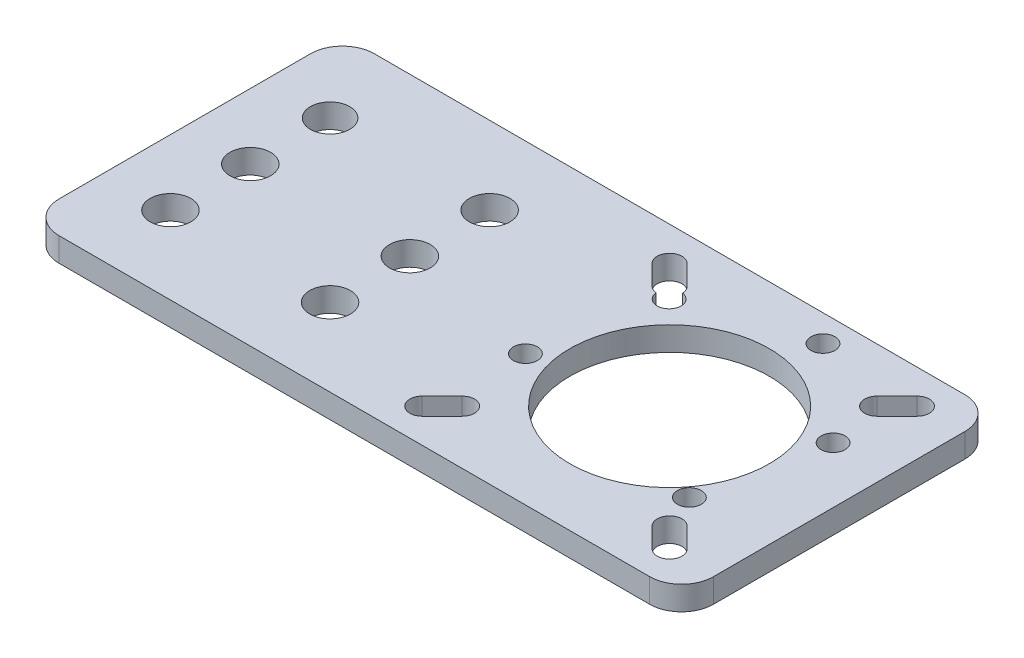
SolidWorks part; units mm, degrees
note: '?' marks a value the reader was unsure of.
ref_plane "Front Plane" through (0, 0, 0) normal (0, 0, 1) x (1, 0, 0)
ref_plane "Top Plane" through (0, 0, 0) normal (0, 1, 0) x (1, 0, 0)
ref_plane "Right Plane" through (0, 0, 0) normal (1, 0, 0) x (0, 0, -1)
sketch "Sketch1" plane through (0, 0, 0) normal (0, 1, 0) x (1, 0, 0)
  line L0 (55.3362, 24.6318) -> (52.8362, 22.1318) construction
  line L1 (-16.9138, 28.8818) -> (57.0862, 28.8818)
  line L2 (-20.9138, 24.8818) -> (-20.9138, -6.6182)
  line L3 (-16.9138, -10.6182) -> (57.0862, -10.6182)
  line L4 (61.0862, 24.8818) -> (61.0862, -6.6182)
  line L10 (56.4322, -5.2721) -> (53.9322, -2.7721)
  line L13 (56.4322, 23.5358) -> (53.9322, 21.0358)
  line L14 (54.2402, 25.7279) -> (51.7402, 23.2279)
  line L15 (18.7976, -10.6182) -> (18.7976, 28.8818) construction
  line L16 (55.3362, -6.3682) -> (52.8362, -3.8682) construction
  line L17 (56.4322, -5.2721) -> (53.9322, -2.7721)
  line L18 (54.2402, -7.4642) -> (51.7402, -4.9642)
  line L19 (54.2402, -7.4642) -> (51.7402, -4.9642)
  line L20 (55.3362, -6.3682) -> (52.8362, -3.8682) construction
  line L21 (25.4322, -7.4642) -> (27.9322, -4.9642)
  line L22 (23.2402, -5.2721) -> (25.7402, -2.7721)
  line L23 (24.3362, -6.3682) -> (26.8362, -3.8682) construction
  line L24 (23.2402, 23.5358) -> (25.7402, 21.0358)
  line L25 (25.4322, 25.7279) -> (27.9322, 23.2279)
  line L26 (24.3362, 24.6318) -> (26.8362, 22.1318) construction
  line L27 (39.8362, 9.1318) -> (52.8362, 22.1318) construction
  line L28 (18.7976, -10.6182) -> (18.7976, 28.8818) construction
  line L29 (18.7976, 9.1318) -> (-20.9138, 9.1318) construction
  circle A0 centre (39.8362, 9.1318) radius 12.5
  arc A1 (57.0862, -10.6182) -> (61.0862, -6.6182) centre (57.0862, -6.6182) ccw
  arc A2 (61.0862, 24.8818) -> (57.0862, 28.8818) centre (57.0862, 24.8818) ccw
  arc A3 (-16.9138, -10.6182) -> (-20.9138, -6.6182) centre (-16.9138, -6.6182) cw
  arc A4 (-16.9138, 28.8818) -> (-20.9138, 24.8818) centre (-16.9138, 24.8818) ccw
  arc A11 (56.4322, 23.5358) -> (54.2402, 25.7279) centre (55.3362, 24.6318) ccw
  arc A12 (51.7402, 23.2279) -> (53.9322, 21.0358) centre (52.8362, 22.1318) ccw
  arc A13 (56.4322, -5.2721) -> (54.2402, -7.4642) centre (55.3362, -6.3682) cw
  arc A14 (51.7402, -4.9642) -> (53.9322, -2.7721) centre (52.8362, -3.8682) cw
  arc A15 (54.2402, -7.4642) -> (56.4322, -5.2721) centre (55.3362, -6.3682) ccw
  arc A16 (53.9322, -2.7721) -> (51.7402, -4.9642) centre (52.8362, -3.8682) ccw
  arc A17 (23.2402, -5.2721) -> (25.4322, -7.4642) centre (24.3362, -6.3682) ccw
  arc A18 (27.9322, -4.9642) -> (25.7402, -2.7721) centre (26.8362, -3.8682) ccw
  arc A19 (25.4322, 25.7279) -> (23.2402, 23.5358) centre (24.3362, 24.6318) ccw
  arc A20 (25.7402, 21.0358) -> (27.9322, 23.2279) centre (26.8362, 22.1318) ccw
  circle A21 centre (7.2862, 19.1318) radius 2.55
  circle A22 centre (-12.7138, 19.1318) radius 2.4667
  circle A23 centre (-12.7138, 9.1318) radius 2.55
  circle A24 centre (7.2862, 9.1318) radius 2.55
  circle A25 centre (-12.7138, -0.8682) radius 2.55
  circle A26 centre (7.2862, -0.8682) radius 2.55
  circle A27 centre (28.1796, 20.7282) radius 1.5
  circle A28 centre (42.6523, 25.5347) radius 1.5
  circle A29 centre (54.0512, 15.4042) radius 1.5
  circle A30 centre (25.1058, 5.7912) radius 1.5
  circle A32 centre (50.9774, 0.4672) radius 1.5
  point P16 (54.0862, 23.3818)
  point P25 (54.0862, -5.1182)
  point P30 (54.0862, -5.1182)
  point P42 (25.5862, -5.1182)
  point P49 (25.5862, 23.3818)
  point P79 (0, 0)
  point P80 (0, 0)
  dimension "D3" = 21.25
  dimension "D5" = 4
  dimension "D6" = 4.25
  dimension "D12" = 9.75
  dimension "D15" = 19.75
  dimension "D1" = 39.5
  dimension "D2" = 82
  dimension "D4" = 19.75
  dimension "D7" = 8.25
  dimension "D8" = 5.75
  dimension "D9" = 6.75
  dimension "D10" = 4
  dimension "D11" = 18.3848
  dimension "D13" = 53.8
  dimension "D14" = 73.8
  dimension "D16" = 29.75
  dimension "D17" = 29.75
extrude "Boss-Extrude1" add sketch "Sketch1" along normal blind 3
sketch "Sketch2" plane through (0, 3, 0) normal (0, 1, 0) x (1, 0, 0)
  line L0 (20.0862, 28.8818) -> (20.0862, -10.6182)
  line L1 (-16.9138, 28.8818) -> (57.0862, 28.8818) construction
  line L2 (-16.9138, -10.6182) -> (57.0862, -10.6182) construction
ref_axis "Axis1" through (20.0862, 3, -28.8818) along (0, 0, 1)?
